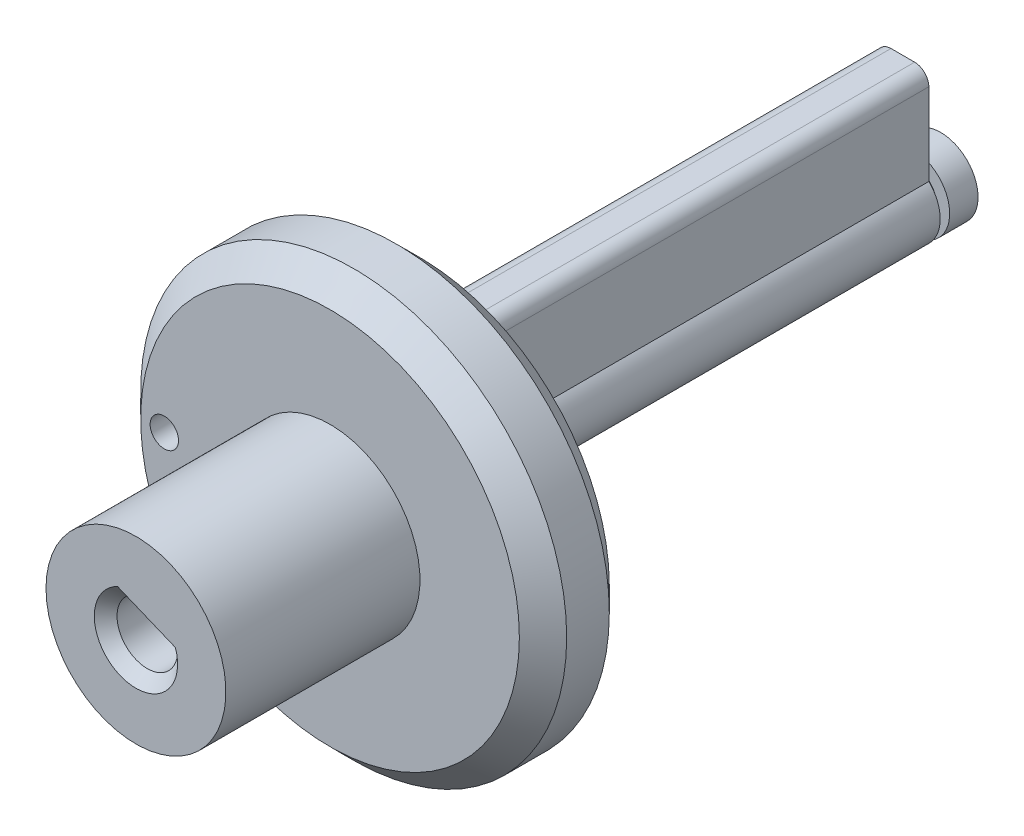
SolidWorks part; units mm, degrees
material "Zinc AG40A (Zn-4Al-0.4Mg; Zamak 3), Cast"
ref_plane "Front Plane" through (0, 0, 0) normal (0, 0, 1) x (1, 0, 0)
ref_plane "Top Plane" through (0, 0, 0) normal (0, 1, 0) x (1, 0, 0)
ref_plane "Right Plane" through (0, 0, 0) normal (1, 0, 0) x (0, 0, -1)
sketch "Sketch1" plane through (0, 0, 0) normal (0, 0, 1) x (1, 0, 0)
  line L0 (-1.2429, 3.556) -> (-1.8135, 0.3198)
  line L1 (-1.2429, 3.556) -> (1.2429, 3.556)
  line L2 (1.2429, 3.556) -> (1.8135, 0.3198)
  line L3 (0, 3.3051) -> (0, 0) construction
  arc A0 (-1.8135, 0.3198) -> (1.8135, 0.3198) centre (0, 0) ccw
  dimension "D1" = 3.683
  dimension "D2" = 10
  dimension "D3" = 10
  dimension "D4" = 3.556
extrude "Extrude1" add sketch "Sketch1" along normal blind 0.0003
sketch "Sketch8" plane through (0, 0, 0.0003) normal (0, 0, 1) x (1, 0, 0)
  circle A2 centre (0, 0) radius 2.413
  dimension "D1" = 4.826
extrude "Extrude8" add sketch "Sketch8" along normal blind 7.62
sketch "Sketch6" plane through (0, 0, 0.0003) normal (0, 0, 1) x (1, 0, 0)
  circle A0 centre (0, 0) radius 5.715
  dimension "D1" = 11.43
extrude "Extrude6" add sketch "Sketch6" along normal blind 2.413
sketch "Sketch4" plane through (0, 0, 7.6203) normal (0, 0, 1) x (1, 0, 0)
  circle A0 centre (0, 0) radius 0.254
  dimension "D1" = 0.508
extrude "Extrude4" cut sketch "Sketch4" against normal blind 6.731
sketch "Sketch5" plane through (0, 0, 0) normal (0, 0, -1) x (-1, 0, 0)
  circle A0 centre (0, 0) radius 1.0033
  dimension "D1" = 2.0066
extrude "Extrude5" add sketch "Sketch5" along normal blind 12.954
fillet "Fillet2" radius 0.889 2 edges at (-1.2429, 3.556, 0.0001) (1.2429, 3.556, 0.0001)
chamfer "Chamfer1" distance 0.635 angle 45 1 edges at (5.715, 0, 0.0003)
chamfer "Chamfer3" distance 0.635 angle 45 1 edges at (5.715, 0, 2.4133)
sketch "Sketch9" plane through (0, 0, 0) normal (0, 0, -1) x (-1, 0, 0)
  line L1 (-0.3175, 3.302) -> (0.3175, 3.302)
  line L2 (-0.6985, 2.921) -> (-0.6985, 0)
  line L3 (-0.6985, 0) -> (0.6985, 0)
  line L4 (0.6985, 2.921) -> (0.6985, 0)
  arc A0 (-0.3175, 3.302) -> (-0.6985, 2.921) centre (-0.3175, 2.921) ccw
  arc A1 (0.3175, 3.302) -> (0.6985, 2.921) centre (0.3175, 2.921) cw
  point P4 (0, 0)
  dimension "D3" = 0.381
  dimension "D1" = 1.397
  dimension "D2" = 3.302
extrude "Extrude9" add sketch "Sketch9" along normal blind 12.954
sketch "Sketch17" plane through (0, 0, 7.6203) normal (0, 0, 1) x (1, 0, 0)
  line L0 (0, 0) -> (0.4411, 1.0649) construction
  line L2 (0, 0) -> (0, 0.8128)
  line L4 (0, 0) -> (0.5747, 0.5747)
  circle A0 centre (0, 0) radius 0.7366 construction
  arc A1 (0.1537, 0.7981) -> (0.4557, 0.673) centre (0.3791, 0.9152) ccw
  arc A3 (0.5747, 0.5747) -> (0.4557, 0.673) centre (0, 0) ccw
  arc A4 (0.1537, 0.7981) -> (0, 0.8128) centre (0, 0) ccw
  dimension "D2" = 45
  dimension "D3" = 22.5
  dimension "D4" = 1.4732
  dimension "D1" = 0.508
  dimension "D6" = 1.6256
extrude "Extrude11" cut sketch "Sketch17" against normal blind 6.731
pattern_circular "CirPattern1" count 8 over 360 about axis through (0, 0, 7.6203) along (0, 0, 1) of "Extrude11"
sketch "Sketch18" plane through (0, 0, 7.6203) normal (0, 0, 1) x (1, 0, 0)
  line L0 (0, 0) -> (-0.3475, 0) construction
  line L1 (-0.5392, 0.6082) -> (0.8113, 0.0488)
  line L2 (-0.5392, 0.6082) -> (-0.3642, 1.0306)
  line L3 (-0.3642, 1.0306) -> (0.9863, 0.4712)
  line L4 (0.8113, 0.0488) -> (0.9863, 0.4712)
  arc A0 (-0.4557, 0.673) -> (-0.673, 0.4557) centre (0, 0) ccw construction
  arc A1 (0.673, 0.4557) -> (0.4557, 0.673) centre (0, 0) ccw construction
  arc A2 (0.7981, -0.1537) -> (0.7981, 0.1537) centre (0, 0) ccw construction
  arc A3 (-0.4599, 0.5754) -> (0.7321, 0.0817) centre (0, 0) cw construction
  arc A4 (0.1537, 0.7981) -> (0.4557, 0.673) centre (0.3791, 0.9152) ccw construction
  dimension "D1" = 0.381
  dimension "D2" = 22.5
extrude "Extrude12" add sketch "Sketch18" against normal up to surface (6.731 mm away) up to face at (0, 0, 0.8893)
chamfer "Chamfer4" distance 0.381 angle 60 1 edges at (0.1361, 0.3285, 7.6203) first distance on face at (-0.0964, -0.2328, 7.6203)
sketch "Sketch19" plane through (0, 0, 7.6203) normal (0, 0, 1) x (1, 0, 0)
  line L0 (0.8113, 0.0488) -> (-0.5392, 0.6082) construction
  line L1 (0.8113, 0.0488) -> (-0.5392, 0.6082)
  arc A0 (-0.7981, 0.1537) -> (-0.7981, -0.1537) centre (0, 0) ccw construction
  arc A1 (-0.5392, 0.6082) -> (0.8113, 0.0488) centre (0, 0) ccw
extrude "Extrude13" cut sketch "Sketch19" against normal blind 0.6604
sketch "Sketch20" plane through (0, 0, 0) normal (1, 0, 0) x (0, 0, -1)
  line L0 (-6.9599, -0.8128) -> (-6.9599, 0)
  line L1 (-6.9599, 0) -> (-6.1471, 0)
  line L2 (-6.1471, 0) -> (-6.9599, -0.8128)
  line L5 (-6.9599, -0.6612) -> (-6.9599, -0.7981) construction
  line L6 (-7.3896, 0) -> (-5.2833, 0) construction
  line L7 (-6.9599, -0.673) -> (-6.9599, -0.7981) construction
  dimension "D1" = 0.8128
  dimension "D2" = 45
revolve "Cut-Revolve1" cut sketch "Sketch20" angle 130 about L6 other way angle 90
ref_plane "Plane1" through (0, 0, 6.9603) normal (0, 0, 1) x (1, 0, 0)
ref_plane "Plane2" through (0, 0, 6.9603) normal (0, 0, 1) x (1, 0, 0)
sketch "Sketch21" plane through (0, 0, 6.9603) normal (0, 0, 1) x (1, 0, 0)
  line L0 (0.8113, 0.0488) -> (-0.5392, 0.6082) construction
  line L1 (-0.4599, 0.5754) -> (-0.5392, 0.6082)
  line L2 (0.7321, 0.0817) -> (0.8113, 0.0488)
  arc A0 (0.7321, 0.0817) -> (-0.4599, 0.5754) centre (0, 0) cw
  arc A1 (0.8113, 0.0488) -> (-0.5392, 0.6082) centre (0, 0) cw
  arc A2 (-0.0356, 0.812) -> (0.5993, 0.549) centre (0, 0) ccw construction
  dimension "D1" = 0.7366
extrude "Boss-Extrude1" add sketch "Sketch21" against normal up to surface (6.0711 mm away) up to face at (-0.0964, -0.2328, 0.8893)
sketch "Sketch22" plane through (0, 0, 6.9603) normal (0, 0, 1) x (1, 0, 0)
  line L2 (-0.4599, 0.5754) -> (-0.5392, 0.6082)
  line L3 (0.8113, 0.0488) -> (0.7321, 0.0817)
  line L4 (-0.4599, 0.5754) -> (-0.5392, 0.6082)
  line L5 (0.8113, 0.0488) -> (0.7321, 0.0817)
  arc A2 (-0.4599, 0.5754) -> (0.7321, 0.0817) centre (0, 0) ccw
  arc A3 (-0.5392, 0.6082) -> (0.8113, 0.0488) centre (0, 0) ccw
  arc A4 (-0.4599, 0.5754) -> (0.7321, 0.0817) centre (0, 0) ccw
  arc A5 (-0.5392, 0.6082) -> (0.8113, 0.0488) centre (0, 0) ccw
  dimension "D1" = 0
extrude "Cut-Extrude1" cut sketch "Sketch22" against normal offset from surface (0.8387 mm away) 1.4986 up to face at (-0.0146, -0.0352, 7.6203)
chamfer "Chamfer5" distance 0.1016 angle 45 1 edges at (-0.2819, -0.6805, 6.1217)
chamfer "Chamfer6" distance 0.3048 angle 45 1 edges at (-0.311, -0.7509, 7.6203)
sketch "Sketch27" plane through (0, 0, 0) normal (0, 0, 1) x (1, 0, 0)
  circle A0 centre (-4.445, 0) radius 0.381
extrude "Cut-Extrude5" cut sketch "Sketch27" along normal through all
sketch "Sketch28" plane through (0, 0, 0.0003) normal (0, 0, -1) x (-1, 0, 0)
  line L0 (4.445, 1.0147) -> (6.1908, 1.4132)
  line L1 (4.445, -1.0147) -> (6.1908, -1.4132)
  arc A0 (4.445, 1.0147) -> (4.445, -1.0147) centre (4.445, 0) ccw
  arc A3 (6.1908, -1.4132) -> (6.1908, 1.4132) centre (0, 0) ccw
extrude "Cut-Extrude7" cut sketch "Sketch28" against normal blind 1.27 contours L0 A3 L1 A0
sketch "Sketch29" plane through (0, 0, -12.954) normal (0, 0, -1) x (-1, 0, 0)
  circle A0 centre (0, 0) radius 0.6604
extrude "Boss-Extrude2" add sketch "Sketch29" along normal blind 1.016
sketch "Sketch30" plane through (0, 0, -13.97) normal (0, 0, -1) x (-1, 0, 0)
  circle A0 centre (0, 0) radius 1.0033
extrude "Boss-Extrude3" add sketch "Sketch30" against normal blind 0.762
